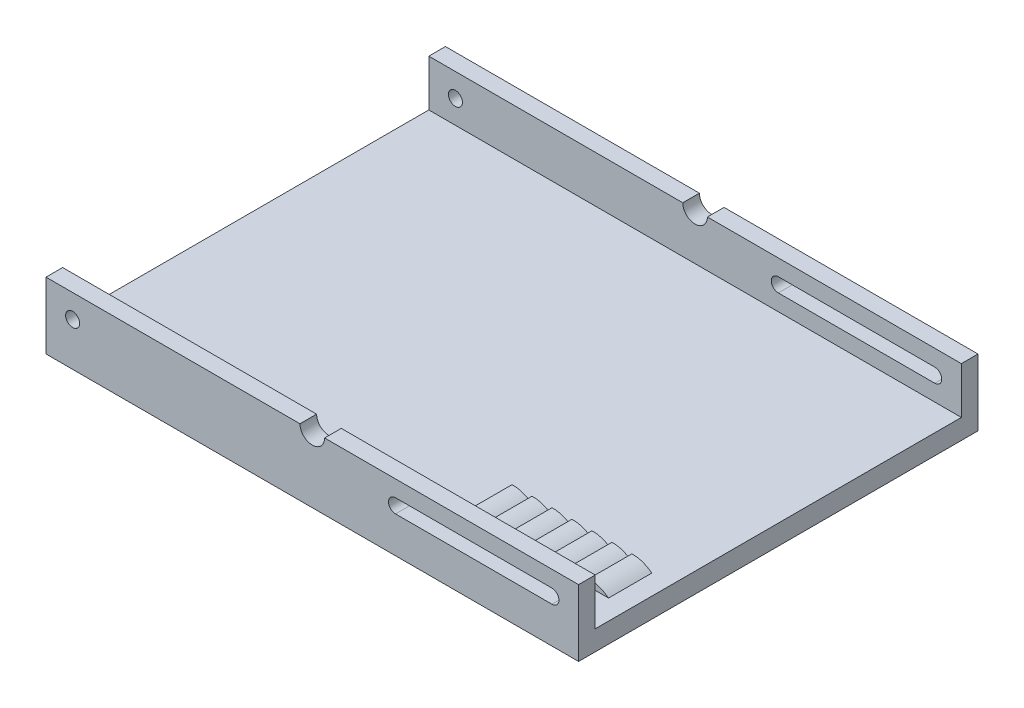
SolidWorks part; units mm, degrees
ref_plane "Vorne" through (0, 0, 0) normal (0, 0, 1) x (1, 0, 0)
ref_plane "Oben" through (0, 0, 0) normal (0, 1, 0) x (1, 0, 0)
ref_plane "Seite" through (0, 0, 0) normal (1, 0, 0) x (0, 0, -1)
sketch "Skizze9" plane through (0, 0, 0) normal (1, 0, 0) x (0, 0, -1)
  line L0 (-60, 20) -> (-60, 0)
  line L1 (-60, 0) -> (60, 0)
  line L2 (60, 0) -> (60, 20)
  line L3 (60, 20) -> (55, 20)
  line L4 (55, 20) -> (55, 6)
  line L5 (55, 6) -> (-55, 6)
  line L6 (-55, 6) -> (-55, 20)
  line L7 (-55, 20) -> (-60, 20)
  dimension "D1" = 120
  dimension "D2" = 5
  dimension "D3" = 20
  dimension "D4" = 14
extrude "Aufsatz-Linear austragen3" add sketch "Skizze9" along normal mid plane 160
sketch "Skizze10" plane through (0, 0, 60) normal (0, 0, 1) x (1, 0, 0)
  line L0 (25, 15.1) -> (72, 15.1)
  line L2 (72, 10.9) -> (25, 10.9)
  line L4 (-80, 20) -> (-80, 0) construction
  line L5 (80, 20) -> (-80, 20) construction
  line L6 (80, 20) -> (80, 0) construction
  circle A0 centre (-72, 13) radius 2.1
  arc A1 (25, 15.1) -> (25, 10.9) centre (25, 13) ccw
  arc A2 (72, 10.9) -> (72, 15.1) centre (72, 13) ccw
  dimension "D2" = 4.2
  dimension "D3" = 7
  dimension "D1" = 8
  dimension "D4" = 8
  dimension "D5" = 47
extrude "Schnitt-Linear austragen1" cut sketch "Skizze10" against normal through all both and the other way through all
sketch "Skizze12" plane through (0, 0, 0) normal (0, 0, 1) x (1, 0, 0)
  line L0 (80, 20) -> (-80, 20) construction
  line L1 (-3.7, 20) -> (3.7, 20)
  arc A0 (-3.7, 20) -> (3.7, 20) centre (0, 20) ccw
  dimension "D1" = 3.7
extrude "Schnitt-Linear austragen2" cut sketch "Skizze12" against normal through all both and the other way through all
sketch "Skizze18" plane through (0, 0, 0) normal (0, 0, -1) x (-1, 0, 0)
  line L1 (-32, 6) -> (-38, 6)
  line L3 (50, 0) -> (-50, 0) construction
  line L37 (-32, 8) -> (-32, 6)
  line L44 (-38, 6) -> (-44, 6) [skipped]
  line L47 (-44, 6) -> (-50, 6) [skipped]
  line L48 (-50, 6) -> (-56, 6) [skipped]
  line L50 (-56, 6) -> (-62, 6) [skipped]
  line L52 (-68, 6) -> (-74, 6) [skipped]
  line L53 (-62, 6) -> (-68, 6) [skipped]
  line L56 (-74, 6) -> (-80, 6) [skipped]
  line L58 (-80, 6) -> (-86, 6) [skipped]
  line L60 (-86, 6) -> (-92, 6) [skipped]
  line L63 (-92, 6) -> (-98, 6) [skipped]
  line L64 (-98, 6) -> (-104, 6) [skipped]
  arc A0 (-25, 10.9) -> (-25, 15.1) centre (-25, 13) ccw construction
  spline S0 degree 2 poles (-38, 6) (-35.1677, 8.1247) (-32, 8) knots 0 0 0 0.477298 0.477298 0.477298
  dimension "D1" = 6
  dimension "D2" = 2
  dimension "D3" = 7
  dimension "D4" = 12
  dimension "D5" = 6
extrude "Aufsatz-Linear austragen4" add sketch "Skizze18" along direction (0, 0, 1) on the side against the normal blind 45
pattern_linear "Lineares Muster1" count 7 spacing 6 along (1, 0, 0) of "Aufsatz-Linear austragen4"
sketch "Skizze19" plane through (0, 0, 0) normal (0, 0, 1) x (1, 0, 0)
  line L0 (-80, 20) -> (-80, 0) construction
  line L1 (80, 20) -> (-80, 20)
  line L2 (80, 20) -> (80, 6)
  line L3 (80, 6) -> (-80, 6)
  line L4 (-80, 20) -> (-80, 6)
  line L5 (0, 6) -> (0, 20) construction
  line L6 (80, 13) -> (-80, 13) construction
  point P660 (0, 13)
  dimension "D1" = 14
extrude "Schnitt-Linear austragen3" cut sketch "Skizze19" along normal blind 32
equation "\"32.5.00mm\"=35"
